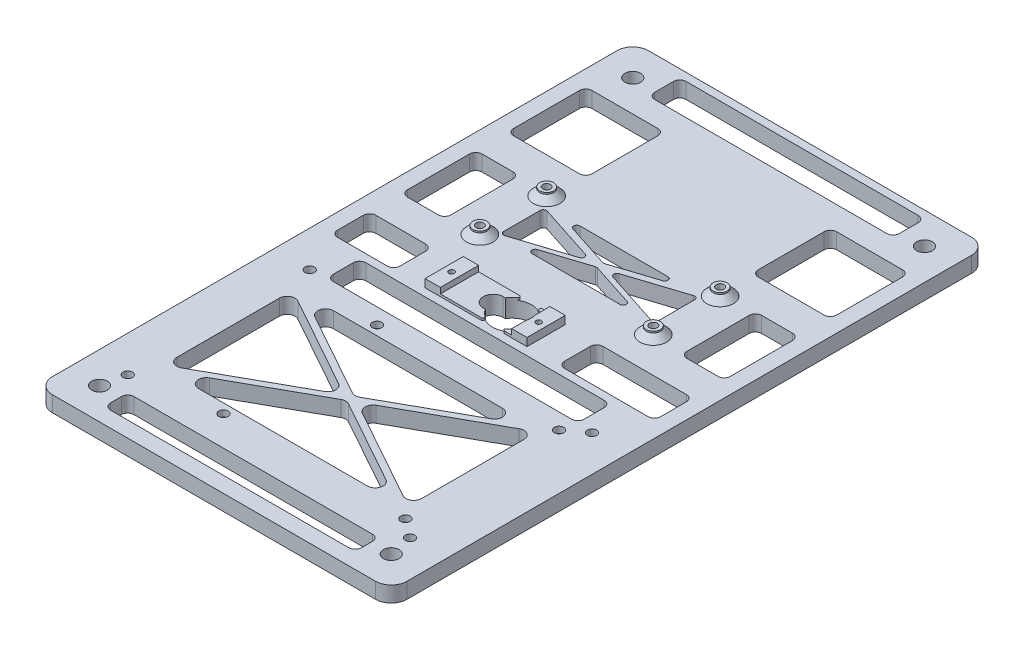
SolidWorks part; units mm, degrees
ref_plane "Front Plane" through (0, 0, 0) normal (0, 0, 1) x (1, 0, 0)
ref_plane "Top Plane" through (0, 0, 0) normal (0, 1, 0) x (1, 0, 0)
ref_plane "Right Plane" through (0, 0, 0) normal (1, 0, 0) x (0, 0, -1)
sketch "Sketch1" plane through (0, 0, 0) normal (0, 1, 0) x (1, 0, 0)
  line L0 (-56.5, -95) -> (-56.5, 95)
  line L1 (-46.5, -85) -> (46.5, -85) construction
  line L2 (-46.5, -85) -> (-46.5, 85) construction
  line L3 (-46.5, 85) -> (46.5, 85) construction
  line L4 (46.5, -85) -> (46.5, 85) construction
  line L5 (-46.5, -85) -> (46.5, 85) construction
  line L6 (-46.5, 85) -> (46.5, -85) construction
  line L7 (-56.5, 95) -> (56.5, 95)
  line L8 (56.5, -95) -> (56.5, 95)
  line L9 (-56.5, -95) -> (56.5, -95)
  circle A0 centre (46.5, 85) radius 2.5
  circle A1 centre (-46.5, 85) radius 2.5
  circle A2 centre (-46.5, -85) radius 2.5
  circle A3 centre (46.5, -85) radius 2.5
  point P0 (0, 0)
  dimension "D3" = 5
  dimension "D1" = 170
  dimension "D2" = 93
  dimension "D4" = 10
extrude "Boss-Extrude1" add sketch "Sketch1" along normal blind 5
fillet "Fillet1" radius 5 4 edges at (-56.5, 2.5, 95) (-56.5, 2.5, -95) (56.5, 2.5, -95) (56.5, 2.5, 95)
sketch "Sketch2" plane through (0, 5, 0) normal (0, 1, 0) x (1, 0, 0)
  line L0 (-39, -24) -> (-39, -73) construction
  line L1 (-39, -24) -> (39, -24) construction
  line L2 (-39, -20.5) -> (39, -20.5) construction
  line L3 (42.5, -48.5) -> (-39, -48.5) construction
  line L4 (-42.5, -24) -> (-42.5, -73) construction
  line L5 (42.5, -24) -> (42.5, -73) construction
  line L6 (-39, -76.5) -> (39, -76.5) construction
  line L7 (0, -20.5) -> (0, -1.8528) construction
  line L8 (-51.5, -95) -> (51.5, -95) construction
  circle A0 centre (39, -24) radius 1.5
  circle A1 centre (39, -73) radius 1.5
  arc A2 (-39, -20.5) -> (-42.5, -24) centre (-39, -24) ccw construction
  arc A3 (-39, -76.5) -> (-42.5, -73) centre (-39, -73) cw construction
  arc A4 (42.5, -24) -> (39, -20.5) centre (39, -24) ccw construction
  arc A5 (42.5, -73) -> (39, -76.5) centre (39, -73) cw construction
  circle A6 centre (-19, -24) radius 1.5
  circle A7 centre (-19, -73) radius 1.5
  point P14 (1.75, -48.5)
  dimension "D1" = 3
  dimension "D2" = 49
  dimension "D3" = 85
  dimension "D4" = 56
  dimension "D5" = 58
  dimension "D6" = 18.5
extrude "Cut-Extrude1" cut sketch "Sketch2" against normal blind 10
sketch "Sketch3" plane through (0, 5, 0) normal (0, 1, 0) x (1, 0, 0)
  line L0 (-45, -80) -> (45, -80) construction
  line L1 (-47.5, -77.5) -> (-47.5, -19.5) construction
  line L2 (-45, -17) -> (45, -17) construction
  line L3 (47.5, -77.5) -> (47.5, -19.5) construction
  line L4 (-47.5, -80) -> (47.5, -17) construction
  line L5 (-47.5, -17) -> (47.5, -80) construction
  line L6 (-51.5, -95) -> (51.5, -95) construction
  circle A0 centre (45, -19.5) radius 1.5
  circle A1 centre (45, -77.5) radius 1.5
  circle A2 centre (-45, -19.5) radius 1.5
  circle A3 centre (-45, -77.5) radius 1.5
  arc A4 (-47.5, -19.5) -> (-45, -17) centre (-45, -19.5) cw construction
  arc A5 (-45, -80) -> (-47.5, -77.5) centre (-45, -77.5) cw construction
  arc A6 (45, -80) -> (47.5, -77.5) centre (45, -77.5) ccw construction
  arc A7 (45, -17) -> (47.5, -19.5) centre (45, -19.5) cw construction
  point P0 (0, -48.5)
  dimension "D3" = 2.5
  dimension "D1" = 95
  dimension "D2" = 63
  dimension "D4" = 15
extrude "Cut-Extrude2" cut sketch "Sketch3" against normal blind 10
sketch "Sketch5" plane through (0, 5, 0) normal (0, 1, 0) x (1, 0, 0)
  line L1 (-38, -90) -> (38, -90)
  line L2 (-40, -88) -> (-40, -84.5)
  line L3 (-38, -82.5) -> (38, -82.5)
  line L4 (40, -88) -> (40, -84.5)
  line L5 (-40, -90) -> (40, -82.5) construction
  line L6 (-40, -82.5) -> (40, -90) construction
  circle A2 centre (-46.5, -85) radius 2.5 construction
  arc A3 (-38, -90) -> (-40, -88) centre (-38, -88) cw
  arc A4 (-40, -84.5) -> (-38, -82.5) centre (-38, -84.5) cw
  arc A5 (38, -82.5) -> (40, -84.5) centre (38, -84.5) cw
  arc A6 (38, -90) -> (40, -88) centre (38, -88) ccw
  point P0 (0, -86.25)
  dimension "D3" = 2
  dimension "D1" = 7.5
  dimension "D2" = 80
extrude "Cut-Extrude4" cut sketch "Sketch5" against normal blind 10
sketch "Sketch6" plane through (0, 5, 0) normal (0, 1, 0) x (1, 0, 0)
  line L0 (6, -6.1) -> (-16.75, -6.1)
  line L1 (6, -6.1) -> (6, 6.1)
  line L2 (6, 6.1) -> (-16.75, 6.1)
  line L3 (-16.75, -6.1) -> (-16.75, 6.1)
  line L4 (6, -6.1) -> (-16.75, 6.1) construction
  line L5 (6, 6.1) -> (-16.75, -6.1) construction
  point P0 (-5.375, 0)
  dimension "D1" = 22.75
  dimension "D2" = 12.2
  dimension "D3" = 6
extrude "Boss-Extrude2" add sketch "Sketch6" along normal blind 0.75
sketch "Sketch13" plane through (0, 5.75, 0) normal (0, 1, 0) x (1, 0, 0)
  line L0 (-5.975, 2.875) -> (-5.2969, 2.875) construction
  line L1 (-5.975, -2.875) -> (-5.2969, -2.875) construction
  line L2 (-5.975, 3.175) -> (-5.3254, 3.175)
  line L3 (-5.975, -3.175) -> (-5.3254, -3.175)
  arc A0 (-5.0816, -2.998) -> (-5.0816, 2.998) centre (0, 0) ccw construction
  arc A1 (-5.975, 2.875) -> (-5.975, -2.875) centre (-5.975, 0) ccw construction
  arc A2 (-5.0816, -2.998) -> (-5.2969, -2.875) centre (-5.2969, -3.125) ccw construction
  arc A3 (-5.0816, 2.998) -> (-5.2969, 2.875) centre (-5.2969, 3.125) cw construction
  arc A4 (-5.3254, -3.175) -> (-5.3254, 3.175) centre (0, 0) ccw
  arc A5 (-5.3254, 3.175) -> (-5.3254, 3.175) centre (-5.3254, 3.175) cw
  arc A6 (-5.975, 3.175) -> (-5.975, -3.175) centre (-5.975, 0) ccw
  arc A7 (-5.3254, -3.175) -> (-5.3254, -3.175) centre (-5.3254, -3.175) ccw
  dimension "D1" = 11.8
  dimension "D3" = 5.75
  dimension "D4" = 0.25
  dimension "D2" = 5.975
  dimension "D5" = 0.3
extrude "Cut-Extrude10" cut sketch "Sketch13" against normal up to next
sketch "Sketch14" plane through (0, 5, 0) normal (0, 1, 0) x (1, 0, 0)
  line L0 (-16.75, -6.1) -> (-1.1091, -6.1) construction
  line L9 (6, 6.1) -> (10.875, 6.1)
  line L10 (6, 6.1) -> (6, 1.562)
  line L11 (6, -6.1) -> (10.875, -6.1)
  line L12 (10.875, 6.1) -> (10.875, -6.1)
  line L13 (-16.75, 6.1) -> (-21.625, 6.1)
  line L14 (-16.75, 6.1) -> (-16.75, -6.1)
  line L15 (-16.75, -6.1) -> (-21.625, -6.1)
  line L16 (-21.625, 6.1) -> (-21.625, -6.1)
  line L17 (6, -1.562) -> (6, -6.1)
  circle A0 centre (-19.25, 0) radius 0.875
  circle A1 centre (8.5, 0) radius 0.875
  arc A2 (6, -1.562) -> (6, 1.562) centre (0, 0) ccw construction
  arc A3 (6, -1.562) -> (6, 1.562) centre (0, 0) ccw
  dimension "D2" = 1.75
  dimension "D1" = 4.875
  dimension "D3" = 2.5
  dimension "D4" = 2.5
extrude "Boss-Extrude3" add sketch "Sketch14" along normal blind 2.55
fillet "Fillet2" radius 0.5 6 edges at (-1.1091, 5.375, 6.1) (1.1091, 5.375, -6.1) (1.1091, 5.375, 6.1) (6, 6.65, 1.562) (6, 6.65, -1.562) (-1.1091, 5.375, -6.1)
sketch "Sketch9" plane through (0, 5, 0) normal (0, 1, 0) x (1, 0, 0)
  line L0 (-48.1787, 10) -> (48.1787, 10)
  line L1 (-50, 11.8213) -> (-50, 38.1787)
  line L2 (-48.1787, 40) -> (48.1787, 40)
  line L3 (50, 11.8213) -> (50, 38.1787)
  line L4 (-50, 10) -> (50, 40) construction
  line L5 (-50, 40) -> (50, 10) construction
  arc A0 (48.1787, 40) -> (50, 38.1787) centre (48.1787, 38.1787) cw
  arc A1 (48.1787, 10) -> (50, 11.8213) centre (48.1787, 11.8213) ccw
  arc A2 (-48.1787, 10) -> (-50, 11.8213) centre (-48.1787, 11.8213) cw
  arc A3 (-50, 38.1787) -> (-48.1787, 40) centre (-48.1787, 38.1787) cw
  point P0 (0, 25)
  dimension "D4" = 1.8213
  dimension "D1" = 30
  dimension "D2" = 100
  dimension "D3" = 25
sketch "Sketch12" plane through (0, 5, 0) normal (0, 1, 0) x (1, 0, 0)
  line L1 (-51.5, 75) -> (-26.5, 75)
  line L2 (-51.5, 75) -> (-51.5, 50)
  line L3 (-51.5, 50) -> (-26.5, 50)
  line L4 (-26.5, 75) -> (-26.5, 50)
  line L6 (0, 0) -> (0, -22.2555) construction
  line L7 (26.5, 75) -> (26.5, 50)
  line L8 (51.5, 50) -> (26.5, 50)
  line L9 (51.5, 75) -> (51.5, 50)
  line L10 (51.5, 75) -> (26.5, 75)
  line L11 (-56.5, 90) -> (-56.5, -90) construction
  dimension "D1" = 25
  dimension "D2" = 25
  dimension "D3" = 50
  dimension "D4" = 5
extrude "Cut-Extrude9" cut sketch "Sketch12" against normal through all
sketch "Sketch15" plane through (0, 5, 0) normal (0, 1, 0) x (1, 0, 0)
  line L0 (-16.75, -6.1) -> (-3.6783, -6.1) construction
  line L1 (-51.5, 6.1) -> (-31.625, 6.1)
  line L2 (-51.5, 6.1) -> (-51.5, -6.1)
  line L3 (-51.5, -6.1) -> (-31.625, -6.1)
  line L4 (-31.625, 6.1) -> (-31.625, -6.1)
  line L5 (-3.6783, 6.1) -> (-21.625, 6.1) construction
  line L6 (-56.5, 90) -> (-56.5, -90) construction
  line L7 (-21.625, 6.1) -> (-21.625, -6.1) construction
  line L8 (-3.6783, 6.1) -> (-16.75, 6.1) construction
  line L9 (20.875, 6.1) -> (51.5, 6.1)
  line L10 (20.875, 6.1) -> (20.875, -6.1)
  line L11 (20.875, -6.1) -> (51.5, -6.1)
  line L12 (51.5, 6.1) -> (51.5, -6.1)
  line L13 (56.5, -90) -> (56.5, 90) construction
  line L14 (10.875, -6.1) -> (10.875, 6.1) construction
  dimension "D1" = 5
  dimension "D2" = 10
  dimension "D3" = 5
  dimension "D4" = 10
extrude "Cut-Extrude11" cut sketch "Sketch15" against normal up to next
fillet "Fillet3" radius 2 16 edges at (-51.5, 2.5, 6.1) (-51.5, 2.5, -6.1) (-31.625, 2.5, -6.1) (-31.625, 2.5, 6.1) (51.5, 2.5, -6.1) (20.875, 2.5, -6.1) (20.875, 2.5, 6.1) (51.5, 2.5, 6.1) (51.5, 2.5, -50) (51.5, 2.5, -75) (26.5, 2.5, -50) (26.5, 2.5, -75) (-26.5, 2.5, -50) (-51.5, 2.5, -50) (-51.5, 2.5, -75) (-26.5, 2.5, -75)
sketch "Sketch16" plane through (0, 0, 0) normal (0, -1, 0) x (1, 0, 0)
  line L0 (-42, 64.8229) -> (-42, 32.1771)
  line L1 (-42.5, 70.5) -> (36.5, 70.5) construction
  line L2 (-42.5, 70.5) -> (-42.5, 26.5) construction
  line L3 (-42.5, 26.5) -> (36.5, 26.5) construction
  line L4 (36.5, 70.5) -> (36.5, 26.5) construction
  line L5 (-42.5, 70.5) -> (36.5, 26.5) construction
  line L6 (-42.5, 26.5) -> (36.5, 70.5) construction
  line L7 (-38.2835, 29.993) -> (-8.9766, 46.3159)
  line L8 (-8.9766, 50.6841) -> (-38.2835, 67.007)
  line L9 (-31.1371, 31.6841) -> (-4.2165, 46.6778)
  line L10 (-1.7835, 46.6778) -> (25.1371, 31.6841)
  line L11 (23.9206, 27) -> (-29.9206, 27)
  line L12 (-3, 48.5) -> (-3, 70.5) construction
  line L13 (-3, 48.5) -> (36.5, 48.5) construction
  line L14 (32.2835, 29.993) -> (2.9766, 46.3159)
  line L15 (36, 64.8229) -> (36, 32.1771)
  line L16 (2.9766, 50.6841) -> (32.2835, 67.007)
  line L17 (-1.7835, 50.3222) -> (25.1371, 65.3159)
  line L18 (-31.1371, 65.3159) -> (-4.2165, 50.3222)
  line L19 (23.9206, 70) -> (-29.9206, 70)
  line L20 (-41.5625, -28.05) -> (-41.5625, -6.1) construction
  line L26 (-27.65, -38.7) -> (27.65, -38.7) construction
  line L27 (-27.65, -38.7) -> (-27.65, -17.4) construction
  line L28 (-49.5, -6.1) -> (-33.625, -6.1) construction
  line L29 (-41.5625, -28.05) -> (-41.5625, -50) construction
  line L30 (51.5, -95) -> (-51.5, -95) construction
  line L31 (-37, -82.5) -> (37, -82.5)
  line L32 (-39, -84.5) -> (-39, -90.5)
  line L33 (-37, -92.5) -> (37, -92.5)
  line L34 (39, -84.5) -> (39, -90.5)
  line L35 (-39, -82.5) -> (39, -92.5) construction
  line L36 (-39, -92.5) -> (39, -82.5) construction
  line L37 (-28.5, -75) -> (-49.5, -75) construction
  line L44 (-49.5, -50) -> (-28.5, -50) construction
  line L63 (-27.65, -17.4) -> (27.65, -17.4) construction
  line L64 (27.65, -38.7) -> (27.65, -17.4) construction
  line L65 (-27.65, -38.7) -> (27.65, -17.4) construction
  line L66 (-27.65, -17.4) -> (27.65, -38.7) construction
  circle A0 centre (-45, 77.5) radius 1.5 construction
  circle A1 centre (39, 73) radius 1.5 construction
  circle A2 centre (39, 24) radius 1.5 construction
  circle A3 centre (-19, 73) radius 1.5 construction
  arc A4 (23.9206, 27) -> (25.1371, 31.6841) centre (23.9206, 29.5) ccw
  arc A5 (-1.7835, 46.6778) -> (-4.2165, 46.6778) centre (-3, 44.4938) ccw
  arc A6 (-29.9206, 27) -> (-31.1371, 31.6841) centre (-29.9206, 29.5) cw
  arc A7 (-42, 32.1771) -> (-38.2835, 29.993) centre (-39.5, 32.1771) ccw
  arc A8 (-8.9766, 46.3159) -> (-8.9766, 50.6841) centre (-10.193, 48.5) ccw
  arc A9 (-38.2835, 67.007) -> (-42, 64.8229) centre (-39.5, 64.8229) ccw
  arc A10 (36, 32.1771) -> (32.2835, 29.993) centre (33.5, 32.1771) cw
  arc A11 (2.9766, 46.3159) -> (2.9766, 50.6841) centre (4.193, 48.5) cw
  arc A12 (32.2835, 67.007) -> (36, 64.8229) centre (33.5, 64.8229) cw
  arc A13 (-1.7835, 50.3222) -> (-4.2165, 50.3222) centre (-3, 52.5062) cw
  arc A14 (23.9206, 70) -> (25.1371, 65.3159) centre (23.9206, 67.5) cw
  arc A15 (-29.9206, 70) -> (-31.1371, 65.3159) centre (-29.9206, 67.5) ccw
  circle A16 centre (-46.5, -85) radius 2.5 construction
  circle A17 centre (46.5, -85) radius 2.5 construction
  arc A30 (-39, -90.5) -> (-37, -92.5) centre (-37, -90.5) ccw
  arc A31 (37, -92.5) -> (39, -90.5) centre (37, -90.5) ccw
  arc A32 (39, -84.5) -> (37, -82.5) centre (37, -84.5) ccw
  arc A33 (-37, -82.5) -> (-39, -84.5) centre (-37, -84.5) ccw
  circle A34 centre (-27.65, -17.4) radius 1.25
  circle A35 centre (27.65, -17.4) radius 1.25
  circle A36 centre (27.65, -38.7) radius 1.25
  circle A37 centre (-27.65, -38.7) radius 1.25
  point P4 (-3, 48.5)
  point P52 (0, -28.05)
  point P69 (0, -87.5)
  dimension "D3" = 2.5
  dimension "D4" = 2.5
  dimension "D11" = 2.5
  dimension "D18" = 2
  dimension "D19" = 2
  dimension "D20" = 2.5
  dimension "D1" = 2.5
  dimension "D2" = 2.5
  dimension "D5" = 1
  dimension "D6" = 1
  dimension "D7" = 1
  dimension "D8" = 1
  dimension "D9" = 1
  dimension "D10" = 1
  dimension "D12" = 55.3
  dimension "D13" = 21.3
  dimension "D14" = 2.5
  dimension "D15" = 7.5
  dimension "D16" = 7.5
  dimension "D17" = 7.5
extrude "Cut-Extrude12" cut sketch "Sketch16" against normal up to next
sketch "Sketch17" plane through (0, 5, 0) normal (0, 1, 0) x (1, 0, 0)
  line L0 (0, 0) -> (0, 50000) construction
  line L1 (-39.65, 39.95) -> (-49.5, 39.95)
  line L2 (-37.65, 37.95) -> (-37.65, 18.15)
  line L3 (-39.65, 16.15) -> (-49.5, 16.15)
  line L4 (-51.5, 37.95) -> (-51.5, 18.15)
  line L5 (-37.65, 39.95) -> (-51.5, 16.15) construction
  line L6 (-37.65, 16.15) -> (-51.5, 39.95) construction
  line L7 (-51.5, 73) -> (-51.5, 52) construction
  line L8 (39.65, 16.15) -> (49.5, 16.15)
  line L9 (51.5, 37.95) -> (51.5, 18.15)
  line L10 (39.65, 39.95) -> (49.5, 39.95)
  line L11 (37.65, 37.95) -> (37.65, 18.15)
  circle A0 centre (-27.65, 17.4) radius 1.25 construction
  circle A1 centre (-27.65, 38.7) radius 1.25 construction
  arc A2 (-51.5, 18.15) -> (-49.5, 16.15) centre (-49.5, 18.15) ccw
  arc A3 (-39.65, 16.15) -> (-37.65, 18.15) centre (-39.65, 18.15) ccw
  arc A4 (-37.65, 37.95) -> (-39.65, 39.95) centre (-39.65, 37.95) ccw
  arc A5 (-49.5, 39.95) -> (-51.5, 37.95) centre (-49.5, 37.95) ccw
  arc A6 (51.5, 18.15) -> (49.5, 16.15) centre (49.5, 18.15) cw
  arc A7 (49.5, 39.95) -> (51.5, 37.95) centre (49.5, 37.95) cw
  arc A8 (39.65, 16.15) -> (37.65, 18.15) centre (39.65, 18.15) cw
  arc A9 (37.65, 37.95) -> (39.65, 39.95) centre (39.65, 37.95) cw
  point P4 (-44.575, 28.05)
  dimension "D2" = 2
  dimension "D1" = 10
extrude "Cut-Extrude13" cut sketch "Sketch17" against normal up to next
sketch "Sketch18" plane through (0, 5, 0) normal (0, 1, 0) x (1, 0, 0)
  line L0 (-24.65, 33.6115) -> (-24.65, 21.9629)
  line L1 (-25.15, 36.2) -> (25.15, 36.2) construction
  line L2 (-25.15, 36.2) -> (-25.15, 19.9) construction
  line L3 (-25.15, 19.9) -> (25.15, 19.9) construction
  line L4 (25.15, 36.2) -> (25.15, 19.9) construction
  line L5 (-25.15, 36.2) -> (25.15, 19.9) construction
  line L6 (-25.15, 19.9) -> (25.15, 36.2) construction
  line L7 (-23.3417, 21.0116) -> (-5.3685, 26.8359)
  line L8 (-5.3685, 28.7385) -> (-23.3417, 34.5628)
  line L9 (-14.0334, 35.7) -> (14.0334, 35.7)
  line L10 (14.3417, 33.7487) -> (0.3083, 29.2011)
  line L11 (-0.3083, 29.2011) -> (-14.3417, 33.7487)
  line L12 (0, 28.05) -> (0, 19.9) construction
  line L13 (0, 28.05) -> (25.15, 28.05) construction
  line L14 (23.3417, 21.0116) -> (5.3685, 26.8359)
  line L15 (24.65, 33.6115) -> (24.65, 21.9629)
  line L16 (5.3685, 28.7385) -> (23.3417, 34.5628)
  line L17 (14.3417, 22.3513) -> (0.3083, 26.8989)
  line L18 (-14.0334, 20.4) -> (14.0334, 20.4)
  line L19 (-0.3083, 26.8989) -> (-14.3417, 22.3513)
  line L20 (-49.5, -6.1) -> (-33.625, -6.1) construction
  line L21 (-38, -8.6) -> (38, -8.6)
  line L22 (-40, -10.6) -> (-40, -17)
  line L23 (-38, -19) -> (38, -19)
  line L24 (40, -10.6) -> (40, -17)
  line L25 (-40, -8.6) -> (40, -19) construction
  line L26 (-40, -19) -> (40, -8.6) construction
  circle A0 centre (-27.65, 38.7) radius 1.25 construction
  circle A1 centre (-27.65, 17.4) radius 1.25 construction
  circle A2 centre (27.65, 38.7) radius 1.25 construction
  arc A3 (-0.3083, 29.2011) -> (0.3083, 29.2011) centre (0, 30.1524) ccw
  arc A4 (14.3417, 33.7487) -> (14.0334, 35.7) centre (14.0334, 34.7) ccw
  arc A5 (-14.0334, 35.7) -> (-14.3417, 33.7487) centre (-14.0334, 34.7) ccw
  arc A6 (-24.65, 21.9629) -> (-23.3417, 21.0116) centre (-23.65, 21.9629) ccw
  arc A7 (-5.3685, 26.8359) -> (-5.3685, 28.7385) centre (-5.6768, 27.7872) ccw
  arc A8 (-23.3417, 34.5628) -> (-24.65, 33.6115) centre (-23.65, 33.6115) ccw
  arc A9 (24.65, 21.9629) -> (23.3417, 21.0116) centre (23.65, 21.9629) cw
  arc A10 (5.3685, 26.8359) -> (5.3685, 28.7385) centre (5.6768, 27.7872) cw
  arc A11 (23.3417, 34.5628) -> (24.65, 33.6115) centre (23.65, 33.6115) cw
  arc A12 (14.3417, 22.3513) -> (14.0334, 20.4) centre (14.0334, 21.4) cw
  arc A13 (-0.3083, 26.8989) -> (0.3083, 26.8989) centre (0, 25.9476) cw
  arc A14 (-14.0334, 20.4) -> (-14.3417, 22.3513) centre (-14.0334, 21.4) cw
  circle A15 centre (-45, -19.5) radius 1.5 construction
  circle A16 centre (45, -19.5) radius 1.5 construction
  circle A17 centre (39, -24) radius 1.5 construction
  arc A18 (38, -8.6) -> (40, -10.6) centre (38, -10.6) cw
  arc A19 (40, -17) -> (38, -19) centre (38, -17) cw
  arc A20 (-38, -19) -> (-40, -17) centre (-38, -17) cw
  arc A21 (-38, -8.6) -> (-40, -10.6) centre (-38, -10.6) ccw
  point P4 (0, 28.05)
  point P54 (0, -13.8)
  dimension "D11" = 1
  dimension "D13" = 5
  dimension "D16" = 2
  dimension "D1" = 2.5
  dimension "D2" = 2.5
  dimension "D3" = 2.5
  dimension "D4" = 2.5
  dimension "D5" = 1
  dimension "D6" = 1
  dimension "D7" = 1
  dimension "D8" = 1
  dimension "D9" = 1
  dimension "D10" = 1
  dimension "D12" = 5
  dimension "D14" = 5
  dimension "D15" = 2.5
extrude "Cut-Extrude14" cut sketch "Sketch18" against normal through all
sketch "Sketch19" plane through (0, 5, 0) normal (0, 1, 0) x (1, 0, 0)
  circle A0 centre (-27.65, 17.4) radius 1.25 construction
  circle A1 centre (27.65, 17.4) radius 1.25 construction
  circle A2 centre (27.65, 38.7) radius 1.25 construction
  circle A3 centre (-27.65, 38.7) radius 1.25 construction
  circle A4 centre (-27.65, 17.4) radius 1.25
  circle A5 centre (27.65, 17.4) radius 1.25
  circle A6 centre (27.65, 38.7) radius 1.25
  circle A7 centre (-27.65, 38.7) radius 1.25
  circle A8 centre (-27.65, 38.7) radius 2.25
  circle A9 centre (-27.65, 17.4) radius 2.25
  circle A10 centre (27.65, 38.7) radius 2.25
  circle A11 centre (27.65, 17.4) radius 2.25
  dimension "D1" = 1
  dimension "D2" = 1
  dimension "D3" = 1
  dimension "D4" = 1
extrude "Boss-Extrude4" add sketch "Sketch19" along normal blind 2.5
chamfer "Chamfer1" distance 2 angle 45 4 edges at (-27.65, 5, -36.45) (-27.65, 5, -15.15) (27.65, 5, -15.15) (27.65, 5, -36.45)
sketch "Sketch20" plane through (0, 0, 0) normal (0, -1, 0) x (1, 0, 0)
  circle A0 centre (-19, 73) radius 2.5
  circle A1 centre (-19, 24) radius 2.5
  circle A2 centre (39, 24) radius 2.5
  circle A4 centre (39, 73) radius 2.5
  dimension "D1" = 5
extrude "Cut-Extrude15" cut sketch "Sketch20" against normal blind 3
